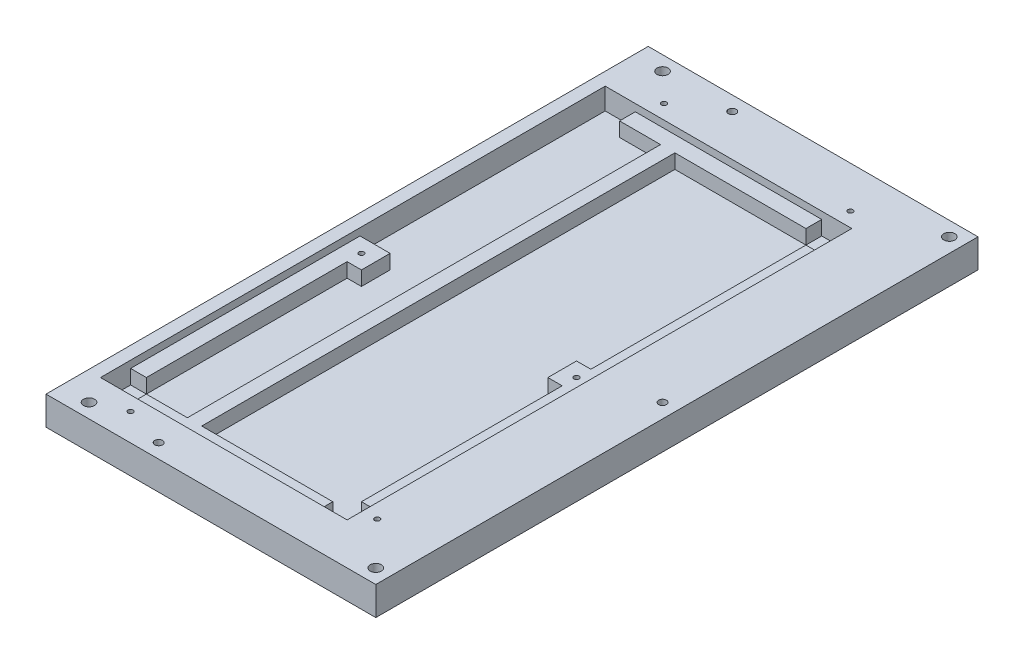
SolidWorks part; units mm, degrees
ref_plane "Front Plane" through (0, 0, 0) normal (0, 0, 1) x (1, 0, 0)
ref_plane "Top Plane" through (0, 0, 0) normal (0, 1, 0) x (1, 0, 0)
ref_plane "Right Plane" through (0, 0, 0) normal (1, 0, 0) x (0, 0, -1)
sketch "Sketch1" plane through (0, 0, 0) normal (0, 1, 0) x (1, 0, 0)
  line L1 (0, 0) -> (146.05, 0)
  line L2 (0, 0) -> (0, 266.7)
  line L3 (0, 266.7) -> (146.05, 266.7)
  line L4 (146.05, 0) -> (146.05, 266.7)
  dimension "D1" = 266.7
  dimension "D2" = 146.05
extrude "Boss-Extrude1" add sketch "Sketch1" along normal blind 12.7
sketch "Sketch2" plane through (0, 12.7, 0) normal (0, 1, 0) x (1, 0, 0)
  line L0 (146.05, 0) -> (146.05, 266.7) construction
  line L1 (5.715, 241.935) -> (114.935, 241.935)
  line L2 (5.715, 241.935) -> (5.715, 18.415)
  line L3 (5.715, 18.415) -> (114.935, 18.415)
  line L4 (114.935, 241.935) -> (114.935, 18.415)
  line L5 (0, 0) -> (146.05, 0) construction
  dimension "D1" = 223.52
  dimension "D2" = 109.22
  dimension "D3" = 31.115
  dimension "D4" = 18.415
extrude "Cut-Extrude1" cut sketch "Sketch2" against normal blind 3.175
sketch "Sketch3" plane through (0, 9.525, 0) normal (0, 1, 0) x (1, 0, 0)
  line L0 (19.05, 25.4) -> (19.05, 18.415)
  line L1 (19.05, 241.935) -> (19.05, 234.95)
  line L2 (19.05, 234.95) -> (37.211, 234.95)
  line L3 (43.561, 25.4) -> (101.6, 25.4)
  line L4 (101.6, 25.4) -> (101.6, 18.415)
  line L5 (43.561, 234.95) -> (101.6, 234.95)
  line L6 (107.95, 31.75) -> (107.95, 120.65)
  line L7 (101.6, 234.95) -> (101.6, 241.935)
  line L8 (107.95, 120.65) -> (101.6, 120.65)
  line L9 (101.6, 120.65) -> (101.6, 133.35)
  line L10 (101.6, 133.35) -> (107.95, 133.35)
  line L11 (107.95, 133.35) -> (107.95, 228.6)
  line L12 (101.6, 241.935) -> (114.935, 241.935)
  line L13 (114.935, 241.935) -> (5.715, 241.935) construction
  line L14 (101.6, 18.415) -> (114.935, 18.415)
  line L15 (114.935, 18.415) -> (114.935, 31.75)
  line L16 (114.935, 18.415) -> (114.935, 241.935) construction
  line L17 (114.935, 31.75) -> (107.95, 31.75)
  line L18 (19.05, 241.935) -> (5.715, 241.935)
  line L19 (5.715, 241.935) -> (5.715, 18.415) construction
  line L20 (5.715, 241.935) -> (5.715, 133.35)
  line L22 (19.05, 18.415) -> (5.715, 18.415)
  line L23 (5.715, 241.935) -> (5.715, 18.415) construction
  line L24 (12.7, 120.65) -> (12.7, 31.75)
  line L25 (5.715, 18.415) -> (5.715, 31.75)
  line L26 (19.05, 25.4) -> (37.211, 25.4)
  line L27 (37.211, 234.95) -> (37.211, 25.4)
  line L28 (114.935, 241.935) -> (114.935, 228.6)
  line L29 (43.561, 25.4) -> (43.561, 234.95)
  line L30 (114.935, 228.6) -> (107.95, 228.6)
  line L31 (5.715, 18.415) -> (114.935, 18.415) construction
  line L32 (5.715, 18.415) -> (114.935, 18.415) construction
  line L33 (5.715, 31.75) -> (12.7, 31.75)
  line L34 (5.715, 133.35) -> (19.05, 133.35)
  line L35 (114.935, 18.415) -> (114.935, 241.935) construction
  line L36 (19.05, 133.35) -> (19.05, 120.65)
  line L37 (19.05, 120.65) -> (12.7, 120.65)
  dimension "D3" = 6.985
  dimension "D4" = 82.55
  dimension "D5" = 6.35
  dimension "D6" = 13.335
  dimension "D7" = 13.335
  dimension "D8" = 13.335
  dimension "D9" = 12.7
  dimension "D10" = 12.7
  dimension "D11" = 95.25
  dimension "D12" = 31.496
  dimension "D13" = 13.335
  dimension "D15" = 13.335
  dimension "D16" = 6.35
  dimension "D17" = 6.985
  dimension "D18" = 6.985
  dimension "D19" = 6.985
  dimension "D20" = 6.35
  dimension "D21" = 6.35
  dimension "D22" = 13.335
  dimension "D23" = 88.9
  dimension "D24" = 6.985
  dimension "D25" = 6.985
extrude "Cut-Extrude2" cut sketch "Sketch3" against normal blind 6.35
hole_wizard "#4-40 Tapped Hole1" positions "Sketch5" profile "Sketch4" tap size "#4-40" standard "ANSI Inch"
sketch "Sketch5" plane through (0, 9.525, 0) normal (0, 1, 0) x (1, 0, 0)
  line L2 (101.6, 120.65) -> (101.6, 133.35) construction
  line L17 (107.95, 120.65) -> (101.6, 120.65) construction
  line L18 (19.05, 120.65) -> (12.7, 120.65) construction
  line L19 (19.05, 133.35) -> (19.05, 120.65) construction
  point P2 (107.95, 127)
  point P53 (12.7, 127)
  point P56 (15.875, 120.65)
  dimension "D1" = 6.35
  dimension "D2" = 6.35
  dimension "D3" = 6.35
  dimension "D4" = 6.35
sketch "Sketch4" plane through (107.95, 9.525, -127) normal (1, 0, 0) x (0, 0, 1)
  line L0 (0, 0) -> (0, 7.0292)
  line L1 (0, 7.0292) -> (1.1303, 6.35)
  line L2 (1.1303, 6.35) -> (1.1303, 0)
  line L5 (1.1303, 0) -> (0, 0)
  line L10 (0, 7.0292) -> (-1.1303, 6.35) construction
  line L11 (0, -6.35) -> (0, 107.95) construction
  dimension "Tap Drill Dia." = 2.2606
  dimension "Tap Drill Depth" = 6.35
  dimension "Drill Angle" = 118
cosmetic thread "Hole Thread5" parameters "D1"=5.588, "D2"=2.8448
cosmetic thread "Hole Thread14" parameters "D1"=5.588, "D2"=2.8448
hole_wizard "#8 Clearance Hole1" positions "Sketch9" profile "Sketch8" hole size "#8" standard "ANSI Inch" end condition through all
sketch "Sketch9" plane through (0, 12.7, 0) normal (0, 1, 0) x (1, 0, 0)
  line L0 (0, 0) -> (146.05, 0) construction
  line L1 (146.05, 0) -> (146.05, 266.7) construction
  line L2 (146.05, 266.7) -> (0, 266.7) construction
  line L3 (0, 266.7) -> (0, 0) construction
  point P0 (12.7, 6.35)
  point P2 (139.7, 6.35)
  point P4 (139.7, 260.35)
  point P6 (12.7, 260.35)
  dimension "D1" = 6.35
  dimension "D2" = 6.35
  dimension "D3" = 6.35
  dimension "D4" = 6.35
  dimension "D5" = 6.35
  dimension "D6" = 6.35
  dimension "D7" = 12.7
  dimension "D8" = 12.7
sketch "Sketch8" plane through (12.7, 12.7, -6.35) normal (1, 0, 0) x (0, 0, 1)
  line L0 (0, 0) -> (0, 12.7)
  line L1 (0, 12.7) -> (2.4574, 12.7)
  line L2 (2.4574, 12.7) -> (2.4574, 0)
  line L5 (2.4574, 0) -> (0, 0)
  line L11 (0, -6.35) -> (0, 107.95) construction
  dimension "Thru Hole Dia." = 4.9149
  dimension "Thru Hole Depth" = 12.7
hole_wizard "#8-32 Tapped Hole1" positions "Sketch11" profile "Sketch12" tap size "#8-32" standard "ANSI Inch"
sketch "Sketch11" plane through (0, 12.7, 0) normal (0, 1, 0) x (1, 0, 0)
  line L0 (37.211, 25.4) -> (37.211, 234.95) construction
  line L1 (146.05, 266.7) -> (0, 266.7) construction
  line L2 (0, 0) -> (146.05, 0) construction
  line L3 (146.05, 0) -> (146.05, 266.7) construction
  point P0 (43.561, 6.35)
  point P2 (43.561, 260.35)
  point P11 (139.7, 133.35)
  dimension "D1" = 6.35
  dimension "D2" = 6.35
  dimension "D3" = 6.35
  dimension "D4" = 6.35
  dimension "D5" = 6.35
  dimension "D6" = 133.35
cosmetic thread "Hole Thread7" parameters "D1"=5.588, "D2"=4.1656
cosmetic thread "Hole Thread8" parameters "D1"=5.588, "D2"=4.1656
cosmetic thread "Hole Thread9" parameters "D1"=5.588, "D2"=4.1656
sketch "Sketch12" plane through (43.561, 12.7, -6.35) normal (1, 0, 0) x (0, 0, 1)
  line L0 (0, 0) -> (0, 10.5628)
  line L1 (0, 10.5628) -> (1.7272, 9.525)
  line L2 (1.7272, 9.525) -> (1.7272, 0)
  line L5 (1.7272, 0) -> (0, 0)
  line L10 (0, 10.5628) -> (-1.7272, 9.525) construction
  line L11 (0, -6.35) -> (0, 107.95) construction
  dimension "Tap Drill Dia." = 3.4544
  dimension "Tap Drill Depth" = 9.525
  dimension "Drill Angle" = 118
hole_wizard "#4-40 Tapped Hole2" positions "Sketch14" profile "Sketch15" tap size "#4-40" standard "ANSI Inch"
sketch "Sketch14" plane through (0, 12.7, 0) normal (0, 1, 0) x (1, 0, 0)
  line L0 (114.935, 18.415) -> (114.935, 241.935) construction
  line L1 (114.935, 241.935) -> (5.715, 241.935) construction
  line L2 (5.715, 18.415) -> (114.935, 18.415) construction
  line L3 (0, 266.7) -> (0, 0) construction
  line L4 (101.6, 241.935) -> (101.6, 234.95) construction
  line L5 (114.935, 31.75) -> (107.95, 31.75) construction
  point P0 (107.95, 248.285)
  point P2 (121.285, 25.4)
  point P11 (25.4, 248.285)
  point P13 (25.4, 12.065)
  dimension "D1" = 6.35
  dimension "D2" = 6.35
  dimension "D3" = 6.35
  dimension "D4" = 6.35
  dimension "D5" = 6.35
  dimension "D6" = 6.35
  dimension "D7" = 25.4
  dimension "D8" = 25.4
sketch "Sketch15" plane through (107.95, 12.7, -248.285) normal (1, 0, 0) x (0, 0, 1)
  line L0 (0, 0) -> (0, 10.3312)
  line L1 (0, 10.3312) -> (1.1303, 9.652)
  line L2 (1.1303, 9.652) -> (1.1303, 0)
  line L5 (1.1303, 0) -> (0, 0)
  line L10 (0, 10.3312) -> (-1.1303, 9.652) construction
  line L11 (0, -6.35) -> (0, 107.95) construction
  dimension "Tap Drill Dia." = 2.2606
  dimension "Tap Drill Depth" = 9.652
  dimension "Drill Angle" = 118
cosmetic thread "Hole Thread10" parameters "D1"=5.588, "D2"=2.8448
cosmetic thread "Hole Thread11" parameters "D1"=5.588, "D2"=2.8448
cosmetic thread "Hole Thread12" parameters "D1"=5.588, "D2"=2.8448
cosmetic thread "Hole Thread13" parameters "D1"=5.588, "D2"=2.8448
